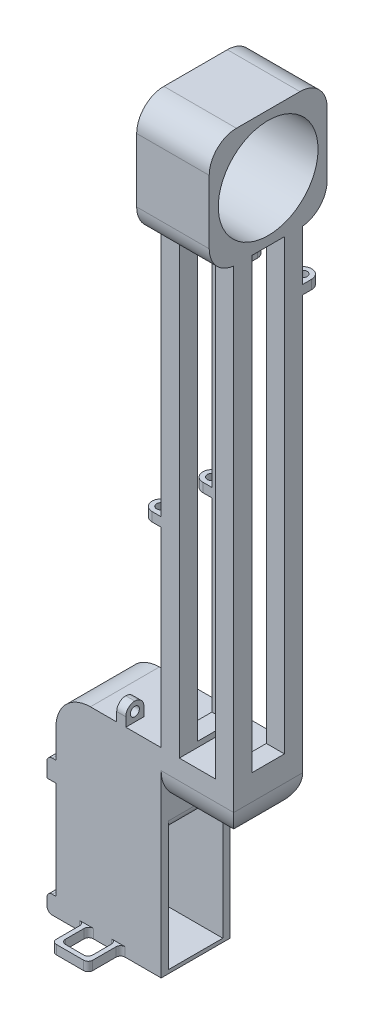
SolidWorks part; units mm, degrees
ref_plane "Front Plane" through (0, 0, 0) normal (0, 0, 1) x (1, 0, 0)
ref_plane "Top Plane" through (0, 0, 0) normal (0, 1, 0) x (1, 0, 0)
ref_plane "Right Plane" through (0, 0, 0) normal (1, 0, 0) x (0, 0, -1)
sketch "Sketch1" plane through (0, 0, 0) normal (1, 0, 0) x (0, 0, -1)
  line L0 (0, 0) -> (-65, -65) construction
  line L1 (0, 0) -> (-65, 0)
  line L2 (0, 0) -> (0, -65)
  line L3 (0, -65) -> (-65, -65)
  line L4 (-65, 0) -> (-65, -65)
  line L5 (-51.5, -65) -> (-13.5, -65)
  line L6 (-51.5, -65) -> (-51.5, -345)
  line L7 (-51.5, -345) -> (-13.5, -345)
  line L8 (-13.5, -65) -> (-13.5, -345)
  circle A0 centre (-32.5, -32.5) radius 27.5
  dimension "D7" = 55
  dimension "D1" = 65
  dimension "D2" = 65
  dimension "D3" = 38
  dimension "D4" = 38
  dimension "D5" = 13.5
  dimension "D6" = 280
extrude "Boss-Extrude1" add sketch "Sketch1" along normal blind 40 contours L0 L1 L4 A0 | L2 L0 A0 L3 | L8 L3 L6 L7 region at (0, -32.5, 0.9192) region at (0, -5.8773, 7.1773) region at (0, -205, 32.5)
fillet "Fillet1" radius 15 4 edges at (20, -65, 0) (20, -65, 65) (20, 0, 0) (20, 0, 65)
sketch "Sketch2" plane through (0, 0, 51.5) normal (0, 0, 1) x (1, 0, 0)
  line L0 (0, -65) -> (0, -345) construction
  line L1 (0, -315) -> (-58, -315)
  line L2 (0, -315) -> (0, -415)
  line L3 (0, -415) -> (-58, -415)
  line L4 (-58, -315) -> (-58, -415)
  line L5 (40, -345) -> (0, -345) construction
  dimension "D1" = 30
  dimension "D2" = 100
  dimension "D3" = 58
extrude "Boss-Extrude2" add sketch "Sketch2" against normal blind 38
fillet "Fillet2" radius 19 4 edges at (40, -345, 32.5) (-58, -315, 32.5)
sketch "Sketch3" plane through (0, 0, 51.5) normal (0, 0, 1) x (1, 0, 0)
  line L0 (40, -65) -> (0, -65) construction
  line L1 (30, -65) -> (10, -65)
  line L2 (30, -65) -> (30, -315)
  line L3 (30, -315) -> (10, -315)
  line L4 (10, -65) -> (10, -315)
  line L5 (0, -326) -> (40, -326) construction
  line L6 (40, -65) -> (40, -326) construction
  line L7 (0, -65) -> (0, -315) construction
  dimension "D1" = 11
  dimension "D2" = 10
  dimension "D3" = 10
extrude "Cut-Extrude1" cut sketch "Sketch3" against normal blind 38
sketch "Sketch4" plane through (40, 0, 0) normal (1, 0, 0) x (0, 0, -1)
  line L0 (-51.5, -326) -> (-13.5, -326) construction
  line L1 (-41.5, -312.0099) -> (-23.5, -312.0099)
  line L2 (-41.5, -312.0099) -> (-41.5, -65)
  line L3 (-41.5, -65) -> (-23.5, -65)
  line L4 (-23.5, -312.0099) -> (-23.5, -65)
  line L5 (-15, 0) -> (-50, 0) construction
  line L6 (-51.5, -65) -> (-51.5, -326) construction
  line L7 (-13.5, -65) -> (-13.5, -326) construction
  dimension "D1" = 13.9901
  dimension "D2" = 65
  dimension "D3" = 10
  dimension "D4" = 10
extrude "Cut-Extrude2" cut sketch "Sketch4" against normal blind 92
sketch "Sketch5" plane through (0, 0, 0) normal (1, 0, 0) x (0, 0, -1)
  line L0 (-13.5, -415) -> (-51.5, -415) construction
  line L1 (-46.5, -410) -> (-18.5, -410)
  line L2 (-46.5, -410) -> (-46.5, -350)
  line L3 (-46.5, -350) -> (-18.5, -350)
  line L4 (-18.5, -410) -> (-18.5, -350)
  line L5 (-51.5, -415) -> (-51.5, -326) construction
  line L6 (-13.5, -415) -> (-13.5, -326) construction
  dimension "D1" = 5
  dimension "D2" = 5
  dimension "D3" = 5
  dimension "D4" = 60
extrude "Cut-Extrude3" cut sketch "Sketch5" against normal blind 58
sketch "Sketch6" plane through (-58, 0, 0) normal (-1, 0, 0) x (0, 0, 1)
  line L0 (13.5, -334) -> (13.5, -415) construction
  line L1 (13.5, -350) -> (51.5, -350)
  line L2 (13.5, -350) -> (13.5, -353)
  line L3 (13.5, -353) -> (51.5, -353)
  line L4 (51.5, -350) -> (51.5, -353)
  line L5 (51.5, -334) -> (51.5, -415) construction
  line L6 (18.5, -350) -> (46.5, -350) construction
  line L8 (13.5, -410) -> (51.5, -410)
  line L9 (13.5, -410) -> (13.5, -407)
  line L10 (13.5, -407) -> (51.5, -407)
  line L11 (51.5, -410) -> (51.5, -407)
  dimension "D1" = 3
  dimension "D2" = 3
  dimension "D3" = 3
  dimension "D4" = 38
  dimension "D5" = 57
extrude "Boss-Extrude11" add sketch "Sketch6" along normal blind 5 separate body
fillet "Fillet3" radius 3 1 edges at (-63, -350, 32.5)
fillet "Fillet4" radius 3 1 edges at (-63, -410, 32.5)
sketch "Sketch7" plane through (0, 0, 0) normal (-1, 0, 0) x (0, 0, 1)
  line L0 (23.5, -312.0099) -> (23.5, -65) construction
  line L1 (23.5, -204.7718) -> (13.5, -204.7718)
  line L2 (23.5, -204.7718) -> (23.5, -209.7718)
  line L3 (23.5, -209.7718) -> (13.5, -209.7718)
  line L4 (13.5, -204.7718) -> (13.5, -209.7718)
  line L5 (13.5, -65) -> (13.5, -315) construction
  line L6 (41.5, -65) -> (41.5, -312.0099) construction
  line L7 (41.5, -204.7718) -> (51.5, -204.7718)
  line L8 (41.5, -204.7718) -> (41.5, -209.7718)
  line L9 (41.5, -209.7718) -> (51.5, -209.7718)
  line L10 (51.5, -204.7718) -> (51.5, -209.7718)
  line L11 (51.5, -65) -> (51.5, -315) construction
  dimension "D1" = 5
  dimension "D2" = 5
extrude "Boss-Extrude14" add sketch "Sketch7" along normal blind 10
sketch "Sketch8" plane through (0, -209.7718, 0) normal (0, -1, 0) x (1, 0, 0)
  line L0 (-10, 23.5) -> (0, 13.5) construction
  line L1 (-10, 51.5) -> (0, 41.5) construction
  circle A0 centre (-5, 18.5) radius 2.5
  circle A1 centre (-5, 46.5) radius 2.5
  dimension "D1" = 5
  dimension "D2" = 5
extrude "Cut-Extrude4" cut sketch "Sketch8" against normal blind 10
fillet "Fillet5" radius 5 4 edges at (-10, -207.2718, 23.5) (-10, -207.2718, 51.5) (-10, -207.2718, 41.5) (-10, -207.2718, 13.5)
sketch "Sketch9" plane through (0, 0, 13.5) normal (0, 0, -1) x (-1, 0, 0)
  line L0 (-30, -315) -> (-30, -65) construction
  line L1 (-30, -92.8284) -> (-40, -92.8284)
  line L2 (-30, -92.8284) -> (-30, -97.8284)
  line L3 (-30, -97.8284) -> (-40, -97.8284)
  line L4 (-40, -92.8284) -> (-40, -97.8284)
  line L5 (-40, -65) -> (-40, -326) construction
  line L6 (-10, -65) -> (-10, -315) construction
  line L7 (-10, -92.8284) -> (0, -92.8284)
  line L8 (-10, -92.8284) -> (-10, -97.8284)
  line L9 (-10, -97.8284) -> (0, -97.8284)
  line L10 (0, -92.8284) -> (0, -97.8284)
  line L11 (0, -65) -> (0, -204.7718) construction
  dimension "D1" = 5
  dimension "D2" = 5
extrude "Boss-Extrude15" add sketch "Sketch9" along normal blind 10
fillet "Fillet6" radius 5 4 edges at (40, -95.3284, 3.5) (30, -95.3284, 3.5) (10, -95.3284, 3.5) (0, -95.3284, 3.5)
sketch "Sketch10" plane through (0, -97.8284, 0) normal (0, -1, 0) x (-1, 0, 0)
  line L0 (-35, -3.5) -> (-35, -13.5) construction
  line L1 (-40, -13.5) -> (-30, -13.5) construction
  line L2 (-5, -3.5) -> (-5, -13.5) construction
  line L3 (-10, -13.5) -> (0, -13.5) construction
  circle A0 centre (-35, -8.5) radius 2.5
  circle A1 centre (-5, -8.5) radius 2.5
  dimension "D1" = 5
  dimension "D2" = 5
extrude "Cut-Extrude5" cut sketch "Sketch10" against normal blind 10
sketch "Sketch11" plane through (0, -315, 0) normal (0, 1, 0) x (1, 0, 0)
  line L0 (0, -13.5) -> (-39, -13.5) construction
  line L1 (-19.5, -13.5) -> (-24.5, -13.5)
  line L2 (-19.5, -13.5) -> (-19.5, -23.5)
  line L3 (-19.5, -23.5) -> (-24.5, -23.5)
  line L4 (-24.5, -13.5) -> (-24.5, -23.5)
  line L5 (0, -51.5) -> (-39, -51.5) construction
  line L6 (-19.5, -51.5) -> (-24.5, -51.5)
  line L7 (-19.5, -51.5) -> (-19.5, -41.5)
  line L8 (-19.5, -41.5) -> (-24.5, -41.5)
  line L9 (-24.5, -51.5) -> (-24.5, -41.5)
  dimension "D1" = 5
  dimension "D2" = 5
  dimension "D3" = 10
  dimension "D4" = 10
extrude "Boss-Extrude16" add sketch "Sketch11" along normal blind 10
fillet "Fillet7" radius 5 4 edges at (-22, -305, 51.5) (-22, -305, 13.5) (-22, -305, 41.5) (-22, -305, 23.5)
sketch "Sketch12" plane through (-24.5, 0, 0) normal (-1, 0, 0) x (0, 0, 1)
  line L0 (18.5, -305) -> (18.5, -315) construction
  line L1 (13.5, -315) -> (23.5, -315) construction
  line L2 (46.5, -305) -> (46.5, -315) construction
  line L3 (41.5, -315) -> (51.5, -315) construction
  circle A0 centre (18.5, -310) radius 2.5
  circle A1 centre (46.5, -310) radius 2.5
  dimension "D1" = 5
  dimension "D2" = 5
extrude "Cut-Extrude7" cut sketch "Sketch12" against normal blind 10
fillet "Fillet9" radius 2 2 edges at (0, -410, 32.5) (0, -350, 32.5)
sketch "Sketch13" plane through (0, -410, 0) normal (0, -1, 0) x (1, 0, 0)
  line L1 (-58, 51.5) -> (-93.8313, 51.5)
  line L2 (-58, 51.5) -> (-58, -9.0861)
  line L3 (-58, -9.0861) -> (-93.8313, -9.0861)
  line L4 (-93.8313, 51.5) -> (-93.8313, -9.0861)
extrude "Cut-Extrude8" cut sketch "Sketch13" against normal blind 10
sketch "Sketch14" plane through (0, -415, 0) normal (0, -1, 0) x (-1, 0, 0)
  line L1 (0, -51.5) -> (58, -51.5)
  line L2 (0, -51.5) -> (0, -13.5)
  line L3 (0, -13.5) -> (58, -13.5)
  line L4 (58, -51.5) -> (58, -13.5)
extrude "Cut-Extrude9" cut sketch "Sketch14" against normal blind 70
sketch "Sketch15" plane through (0, -345, 0) normal (0, -1, 0) x (-1, 0, 0)
  line L1 (0, -51.5) -> (58, -51.5)
  line L2 (0, -51.5) -> (0, -13.5)
  line L3 (0, -13.5) -> (58, -13.5)
  line L4 (58, -51.5) -> (58, -13.5)
extrude "Boss-Extrude17" add sketch "Sketch15" along normal blind 80
sketch "Sketch16" plane through (0, 0, 0) normal (1, 0, 0) x (0, 0, -1)
  line L0 (-13.5, -425) -> (-51.5, -425) construction
  line L1 (-49.5, -423) -> (-15.5, -423)
  line L2 (-49.5, -423) -> (-49.5, -353)
  line L3 (-49.5, -353) -> (-15.5, -353)
  line L4 (-15.5, -423) -> (-15.5, -353)
  line L5 (-51.5, -425) -> (-51.5, -326) construction
  line L6 (-13.5, -425) -> (-13.5, -326) construction
  dimension "D1" = 2
  dimension "D2" = 2
  dimension "D3" = 2
  dimension "D4" = 72
extrude "Cut-Extrude10" cut sketch "Sketch16" against normal blind 58
sketch "Sketch17" plane through (0, -353, 0) normal (0, -1, 0) x (1, 0, 0)
  line L1 (-58, 51.5) -> (-63, 51.5)
  line L2 (-58, 51.5) -> (-58, 13.5)
  line L3 (-58, 13.5) -> (-63, 13.5)
  line L4 (-63, 51.5) -> (-63, 13.5)
extrude "Boss-Extrude18" add sketch "Sketch17" along normal blind 5
sketch "Sketch18" plane through (-58, 0, 0) normal (-1, 0, 0) x (0, 0, 1)
  line L0 (13.5, -425) -> (13.5, -358) construction
  line L1 (51.5, -425) -> (13.5, -425)
  line L2 (51.5, -425) -> (51.5, -415)
  line L3 (51.5, -415) -> (13.5, -415)
  line L4 (13.5, -425) -> (13.5, -415)
  dimension "D1" = 10
extrude "Boss-Extrude19" add sketch "Sketch18" along normal blind 5
fillet "Fillet10" radius 3 2 edges at (-63, -415, 32.5) (-63, -425, 32.5)
fillet "Fillet11" radius 5 1 edges at (0, -353, 32.5)
sketch "Sketch19" plane through (0, 0, 0) normal (1, 0, 0) x (0, 0, -1)
  line L0 (-49.5, -423) -> (-15.5, -423) construction
  line L1 (-49.5, -348) -> (-47.5, -348)
  line L2 (-49.5, -348) -> (-49.5, -423)
  line L3 (-49.5, -423) -> (-47.5, -423)
  line L4 (-47.5, -348) -> (-47.5, -423)
  line L6 (-15.5, -348) -> (-17.5, -348)
  line L7 (-15.5, -348) -> (-15.5, -423)
  line L8 (-15.5, -423) -> (-17.5, -423)
  line L9 (-17.5, -348) -> (-17.5, -423)
  dimension "D1" = 2
  dimension "D2" = 2
extrude "Boss-Extrude22" add sketch "Sketch19" against normal blind 58
sketch "Sketch26" plane through (0, 0, 0) normal (1, 0, 0) x (0, 0, -1)
  line L1 (-47.5, -348) -> (-17.5, -348)
  line L2 (-47.5, -348) -> (-47.5, -357)
  line L3 (-47.5, -357) -> (-17.5, -357)
  line L4 (-17.5, -348) -> (-17.5, -357)
  dimension "D1" = 30
  dimension "D2" = 9
extrude "Boss-Extrude23" add sketch "Sketch26" against normal blind 58
fillet "Fillet12" radius 5 1 edges at (0, -357, 32.5)
sketch "Sketch27" plane through (0, -358, 0) normal (0, -1, 0) x (1, 0, 0)
  line L1 (-58, 51.5) -> (-63, 51.5)
  line L2 (-58, 51.5) -> (-58, 13.5)
  line L3 (-58, 13.5) -> (-63, 13.5)
  line L4 (-63, 51.5) -> (-63, 13.5)
extrude "Boss-Extrude24" add sketch "Sketch27" along normal blind 3
sketch "Sketch30" plane through (0, -425, 0) normal (0, -1, 0) x (-1, 0, 0)
  line L0 (0, -51.5) -> (60, -51.5) construction
  line L1 (42.4238, -51.5) -> (22.3743, -51.5)
  line L2 (42.4238, -51.5) -> (42.4238, -69.3645)
  line L3 (42.4238, -69.3645) -> (22.3743, -69.3645)
  line L4 (22.3743, -51.5) -> (22.3743, -69.3645)
  line L6 (39.9238, -51.5) -> (24.8743, -51.5)
  line L7 (39.9238, -51.5) -> (39.9238, -66.8645)
  line L8 (39.9238, -66.8645) -> (24.8743, -66.8645)
  line L9 (24.8743, -51.5) -> (24.8743, -66.8645)
  dimension "D1" = 2.5
  dimension "D2" = 2.5
  dimension "D3" = 2.5
extrude "Boss-Extrude26" add sketch "Sketch30" against normal blind 5 contours L9 L0 L4 L3 L2 L7 L8 region at (-23.6243, -425, 51.7685)
fillet "Fillet13" radius 2.5 6 edges at (-39.9238, -422.5, 51.5) (-22.3743, -422.5, 51.5) (-24.8743, -422.5, 51.5) (-42.4238, -422.5, 51.5) (-22.3743, -422.5, 69.3645) (-42.4238, -422.5, 69.3645)
fillet "Fillet14" radius 2.5 2 edges at (-39.9238, -422.5, 66.8645) (-24.8743, -422.5, 66.8645)
